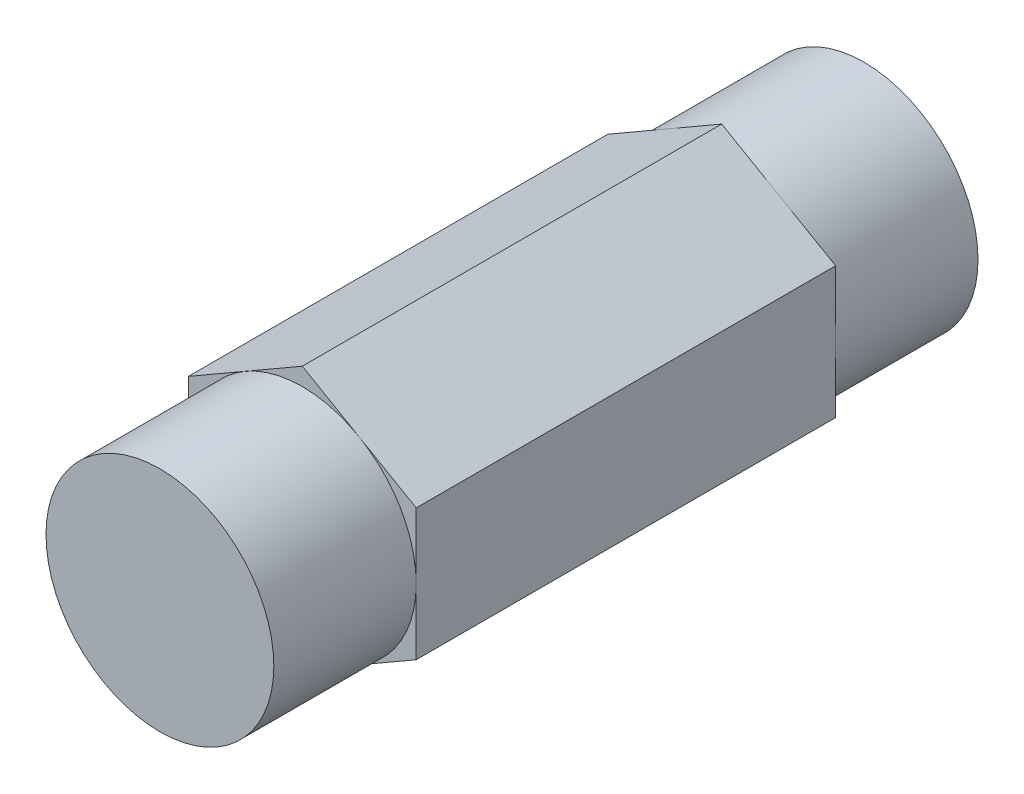
SolidWorks part; units mm, degrees
material "7075-T6 (SN)"
ref_plane "Front Plane" through (0, 0, 0) normal (0, 0, 1) x (1, 0, 0)
ref_plane "Top Plane" through (0, 0, 0) normal (0, 1, 0) x (1, 0, 0)
ref_plane "Right Plane" through (0, 0, 0) normal (1, 0, 0) x (0, 0, -1)
sketch "Sketch1" plane through (0, 0, 0) normal (0, 0, 1) x (1, 0, 0)
  line L1 (0, 7.3323) -> (-6.35, 3.6662)
  line L2 (-6.35, 3.6662) -> (-6.35, -3.6662)
  line L3 (-6.35, -3.6662) -> (0, -7.3323)
  line L4 (0, -7.3323) -> (6.35, -3.6662)
  line L5 (6.35, -3.6662) -> (6.35, 3.6662)
  line L6 (6.35, 3.6662) -> (0, 7.3323)
  circle A0 centre (0, 0) radius 6.35 construction
  dimension "D1" = 12.7
extrude "Boss-Extrude1" add sketch "Sketch1" along normal mid plane 39.2557
sketch "Sketch2" plane through (0, 0, -19.6279) normal (0, 0, -1) x (-1, 0, 0)
  circle A0 centre (0, 0) radius 6.35
  dimension "D1" = 12.7
extrude "Cut-Extrude-Thin1" cut sketch "Sketch2" against normal blind 7.9375 thin thin type one direction wall 2.54
mirror "Mirror1" about plane through (0, 0, 0) normal (0, 0, 1) of "Cut-Extrude-Thin1"
